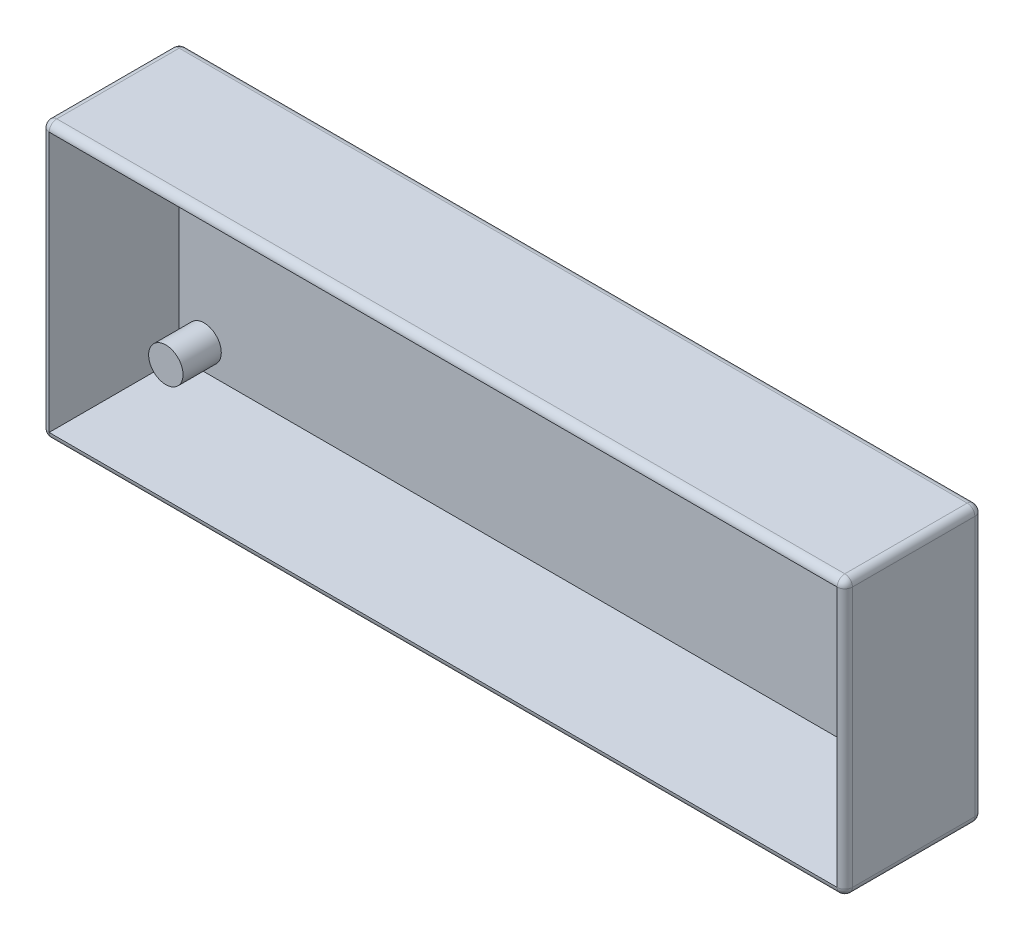
SolidWorks part; units mm, degrees
ref_plane "Front Plane" through (0, 0, 0) normal (0, 0, 1) x (1, 0, 0)
ref_plane "Top Plane" through (0, 0, 0) normal (0, 1, 0) x (1, 0, 0)
ref_plane "Right Plane" through (0, 0, 0) normal (1, 0, 0) x (0, 0, -1)
sketch "Sketch2" plane through (0, 0, 0) normal (0, 0, 1) x (1, 0, 0)
  line L0 (-52.5, -18) -> (52.5, 18) construction
  line L1 (-52.5, 18) -> (52.5, 18)
  line L2 (-52.5, 18) -> (-52.5, -18)
  line L3 (-52.5, -18) -> (52.5, -18)
  line L4 (52.5, 18) -> (52.5, -18)
  line L5 (52.5, -18) -> (-52.5, 18) construction
  point P4 (0, 0)
  dimension "D1" = 36
  dimension "D2" = 105
extrude "Boss-Extrude1" add sketch "Sketch2" along normal mid plane 18
shell "Shell1" thickness 1 removed face at (0, 0, 9)
sketch "Sketch3" plane through (0, 0, -8) normal (0, 0, 1) x (1, 0, 0)
  line L0 (-51.5, 17) -> (-51.5, -17) construction
  line L1 (52.5, 18) -> (-52.5, 18) construction
  line L2 (-48.25, 13.5) -> (48.3377, 13.5877) construction
  line L3 (48.3377, 13.5877) -> (48.3377, -13.6297) construction
  circle A0 centre (-48.25, 13.5) radius 2.25
  circle A1 centre (48.3377, 13.5877) radius 2.25
  circle A2 centre (48.3377, -13.6297) radius 2.25
  circle A3 centre (-48.25, -13.7174) radius 2.25
  dimension "D1" = 4.5
  dimension "D2" = 3.25
  dimension "D3" = 4.5
  dimension "D7" = 27.2174
  dimension "D6" = 96.5877
  dimension "D4" = 2
  dimension "D5" = 2
extrude "Boss-Extrude2" add sketch "Sketch3" along normal blind 5
fillet "Fillet1" radius 1 12 edges at (52.5, 0, 9) (0, 18, 9) (0, -18, 9) (-52.5, 0, 9) (0, -18, -9) (-52.5, 0, -9) (52.5, 0, -9) (0, 18, -9) (52.5, 18, 0) (-52.5, -18, 0) (52.5, -18, 0) (-52.5, 18, 0)
sketch "Sketch5" plane through (0, -18, 0) normal (0, -1, 0) x (1, 0, 0)
  line L0 (-15, -6) -> (15, -6) construction
  line L2 (-51.5, -8) -> (51.5, -8) construction
  text T0 "<b>GritMaker V1.0</b>"
  point P2 (-7.8613, -6)
  point P3 (-23.7586, -6)
  point P7 (-16.9277, -6)
  point P8 (0, 0)
  dimension "D1" = 30
  dimension "D2" = 2
  dimension "D3" = 15
extrude "Cut-Extrude3" cut sketch "Sketch5" against normal blind 0.5
